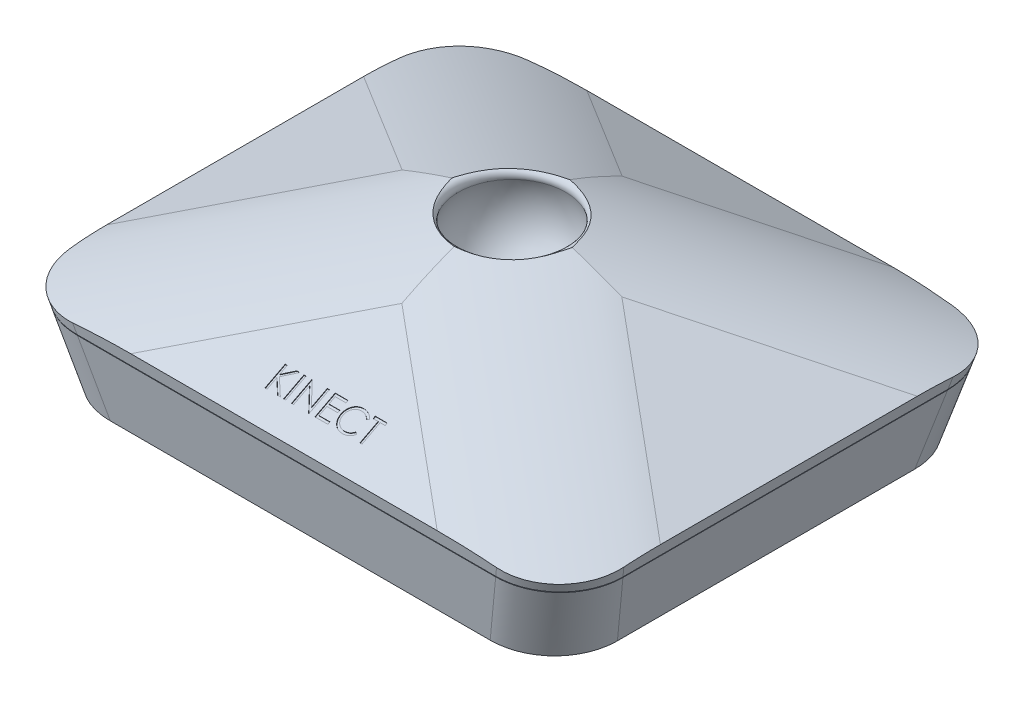
SolidWorks part; units mm, degrees
ref_plane "Front Plane" through (0, 0, 0) normal (0, 0, 1) x (1, 0, 0)
ref_plane "Top Plane" through (0, 0, 0) normal (0, 1, 0) x (1, 0, 0)
ref_plane "Right Plane" through (0, 0, 0) normal (1, 0, 0) x (0, 0, -1)
sketch "Sketch1" plane through (0, 0, 0) normal (0, 1, 0) x (1, 0, 0)
  line L1 (-42.5, 35) -> (42.5, 35)
  line L2 (-42.5, 35) -> (-42.5, -35)
  line L3 (-42.5, -35) -> (42.5, -35)
  line L4 (42.5, 35) -> (42.5, -35)
  line L5 (-42.5, 35) -> (42.5, -35) construction
  line L6 (-42.5, -35) -> (42.5, 35) construction
  point P0 (0, 0)
extrude "Boss-Extrude1" add sketch "Sketch1" along normal blind 26
sketch "Sketch2" plane through (0, 0, 35) normal (0, 0, 1) x (1, 0, 0)
  line L0 (-39, 0) -> (-42.5, 0)
  line L1 (-42.5, 0) -> (42.5, 0) construction
  line L2 (39, 0) -> (42.5, 0)
  line L4 (42.5, 26) -> (42.5, 0) construction
  line L5 (-42.5, 26) -> (-42.5, 0) construction
  line L6 (-42.5, 13) -> (-39, 0)
  line L7 (-42.5, 0) -> (-42.5, 13)
  line L8 (42.5, 13) -> (39, 0)
  line L9 (42.5, 0) -> (42.5, 13)
extrude "Cut-Extrude1" cut sketch "Sketch2" against normal through all
sketch "Sketch3" plane through (0, 0, 35) normal (0, 0, 1) x (1, 0, 0)
  line L0 (-10, 26) -> (-42.5, 13)
  line L1 (-42.5, 26) -> (42.5, 26) construction
  line L3 (-42.5, 13) -> (-42.5, 26)
  line L4 (-42.5, 26) -> (-10, 26)
  line L5 (10, 26) -> (42.5, 13)
  line L6 (42.5, 13) -> (42.5, 26)
  line L7 (42.5, 26) -> (10, 26)
extrude "Cut-Extrude2" cut sketch "Sketch3" against normal through all
sketch "Sketch4" plane through (0, 0, 0) normal (1, 0, 0) x (0, 0, -1)
  line L0 (32.5, 0) -> (35, 13)
  line L1 (35, 0) -> (-35, 0) construction
  line L3 (35, 13) -> (35, 0)
  line L4 (35, 0) -> (32.5, 0)
  line L5 (-32.5, 0) -> (-35, 13)
  line L6 (-35, 13) -> (-35, 0)
  line L7 (-35, 0) -> (-32.5, 0)
extrude "Cut-Extrude3" cut sketch "Sketch4" against normal through all and the other way through all
sketch "Sketch5" plane through (0, 0, 0) normal (1, 0, 0) x (0, 0, -1)
  line L0 (10, 26) -> (35, 13)
  line L1 (35, 26) -> (-35, 26) construction
  line L3 (35, 13) -> (35, 26)
  line L4 (35, 26) -> (10, 26)
  line L5 (-10, 26) -> (-35, 13)
  line L6 (-35, 13) -> (-35, 26)
  line L7 (-35, 26) -> (-10, 26)
extrude "Cut-Extrude4" cut sketch "Sketch5" against normal through all and the other way through all
sketch "Sketch7" plane through (0, 26, 0) normal (0, 1, 0) x (1, 0, 0)
  line L1 (-2.5, 2.5) -> (2.5, 2.5)
  line L2 (-2.5, 2.5) -> (-2.5, -2.5)
  line L3 (-2.5, -2.5) -> (2.5, -2.5)
  line L4 (2.5, 2.5) -> (2.5, -2.5)
  line L5 (-2.5, 2.5) -> (2.5, -2.5) construction
  line L6 (-2.5, -2.5) -> (2.5, 2.5) construction
  point P0 (0, 0)
extrude "Cut-Extrude5" cut sketch "Sketch7" against normal blind 5
sketch "Sketch8" plane through (0, 21, 0) normal (0, 1, 0) x (1, 0, 0)
  line L0 (-17.1014, 0) -> (19.9364, 0) construction
  line L1 (-9, 0) -> (9, 0)
  arc A0 (9, 0) -> (-9, 0) centre (0, 0) ccw
revolve "Cut-Revolve3" cut sketch "Sketch8" angle 360 about L0
fillet "Fillet1" radius 40 4 edges at (26.25, 19.5, -22.5) (-26.25, 19.5, -22.5) (-26.25, 19.5, 22.5) (26.25, 19.5, 22.5)
fillet "Fillet2" radius 10 4 edges at (-40.5078, 5.6003, -33.577) (40.5078, 5.6003, -33.577) (40.5078, 5.6003, 33.577) (-40.5078, 5.6003, 33.577)
fillet "Fillet3" radius 1 1 edges at (0, 26, 7.4833)
sketch "Sketch9" plane through (0, 24.5592, 12.7708) normal (0, 0.8872, 0.4614) x (1, 0, 0)
  text T0 "KINECT"
extrude "Cut-Extrude6" cut sketch "Sketch9" against normal blind 0.1
sketch "Sketch10" plane through (0, 0, 0) normal (0, -1, 0) x (1, 0, 0)
  line L0 (-29.1523, 31.8032) -> (29.1523, 31.8032)
  line L1 (-38.1307, 22.8167) -> (-38.1307, -22.8167)
  line L2 (29.1523, -31.8032) -> (-29.1523, -31.8032)
  line L3 (38.1307, -22.8167) -> (38.1307, 22.8167)
  arc A0 (-29.1523, 31.8032) -> (-38.1307, 22.8167) centre (-28.6439, 22.3168) ccw
  arc A1 (-38.1307, -22.8167) -> (-29.1523, -31.8032) centre (-28.6439, -22.3168) ccw
  arc A2 (29.1523, -31.8032) -> (38.1307, -22.8167) centre (28.6439, -22.3168) ccw
  arc A3 (38.1307, 22.8167) -> (29.1523, 31.8032) centre (28.6439, 22.3168) ccw
  dimension "D1" = 19
  dimension "D2" = 19
  dimension "D3" = 19
  dimension "D4" = 19
extrude "Boss-Extrude2" add sketch "Sketch10" along normal blind 0.5
sketch "Sketch11" plane through (0, 0, 0) normal (0, 0, 1) x (1, 0, 0)
  line L3 (-47.5, 11.05) -> (47.5, 11.05)
  line L4 (-47.5, 11.05) -> (-47.5, 10.95)
  line L5 (-47.5, 10.95) -> (47.5, 10.95)
  line L6 (47.5, 11.05) -> (47.5, 10.95)
  line L7 (-47.5, 11.05) -> (47.5, 10.95) construction
  line L8 (-47.5, 10.95) -> (47.5, 11.05) construction
extrude "Cut-Extrude7" cut sketch "Sketch11" against normal blind 10 from offset 35
mirror "Mirror1" about plane through (0, 0, 0) normal (0, 0, 1) of "Cut-Extrude7"
sketch "Sketch12" plane through (0, 0, 0) normal (1, 0, 0) x (0, 0, -1)
  line L3 (25, 10.95) -> (-25, 10.95)
  line L4 (25, 10.95) -> (25, 11.05)
  line L5 (25, 11.05) -> (-25, 11.05)
  line L6 (-25, 10.95) -> (-25, 11.05)
  line L7 (25, 10.95) -> (-25, 11.05) construction
  line L8 (25, 11.05) -> (-25, 10.95) construction
extrude "Cut-Extrude8" cut sketch "Sketch12" against normal blind 1 from offset 42.5
mirror "Mirror2" about plane through (0, 0, 0) normal (1, 0, 0) of "Cut-Extrude8"
